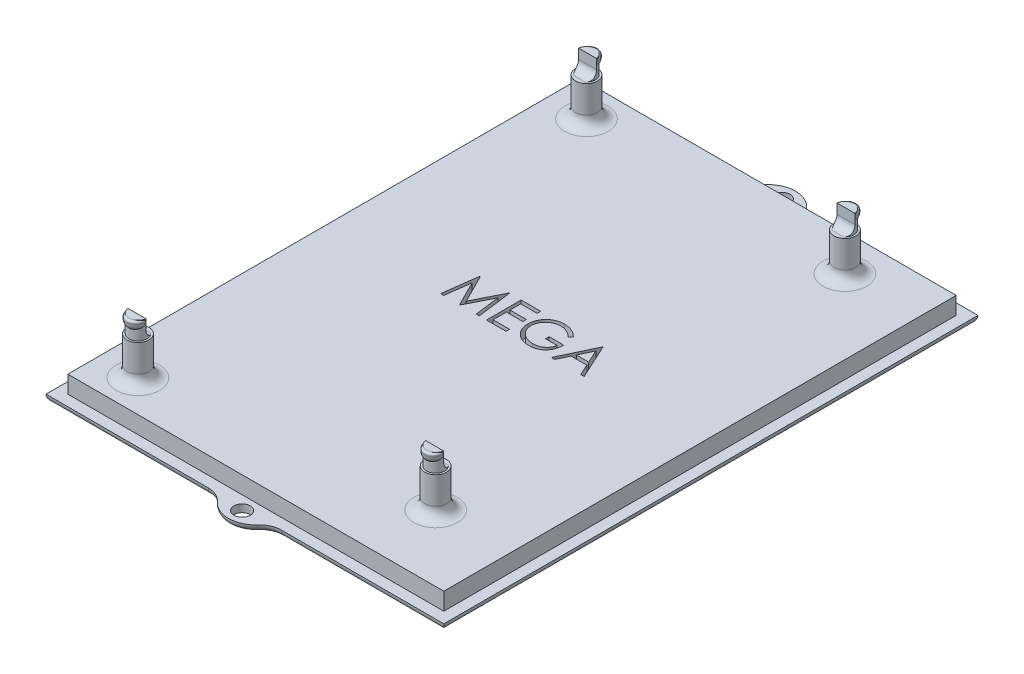
SolidWorks part; units mm, degrees
ref_plane "Front Plane" through (0, 0, 0) normal (0, 0, 1) x (1, 0, 0)
ref_plane "Top Plane" through (0, 0, 0) normal (0, 1, 0) x (1, 0, 0)
ref_plane "Right Plane" through (0, 0, 0) normal (1, 0, 0) x (0, 0, -1)
sketch "Sketch1" plane through (0, 0, 0) normal (0, 1, 0) x (1, 0, 0)
  line L0 (-34.45, 46.95) -> (34.45, 46.95)
  line L5 (-34.45, 46.95) -> (-34.45, -46.95)
  line L6 (-34.45, -46.95) -> (34.45, -46.95)
  line L7 (34.45, 46.95) -> (34.45, -46.95)
  point P11 (-34.45, 0)
  point P12 (0, -46.95)
  dimension "D3" = 93.9
  dimension "D4" = 68.9
extrude "Boss-Extrude1" add sketch "Sketch1" along normal blind 4.575
sketch "Sketch2" plane through (0, 4.575, 0) normal (0, 1, 0) x (1, 0, 0)
  line L0 (-27.45, 41.1) -> (20.81, 41.1) construction
  line L1 (-27.45, 41.1) -> (-27.45, -41.1) construction
  line L2 (20.81, 41.1) -> (20.81, 40.2) construction
  line L3 (20.81, -34.8) -> (-27.45, -34.8) construction
  line L4 (-34.45, 46.95) -> (-34.45, -46.95) construction
  line L6 (20.81, 40.2) -> (20.81, -34.8) construction
  circle A12 centre (-27.45, -41.1) radius 2
  circle A13 centre (-27.45, 41.1) radius 2
  circle A14 centre (20.81, 40.2) radius 2
  circle A15 centre (20.81, -34.8) radius 2
  point P3 (-27.45, 0)
  dimension "D7" = 7
  dimension "D6" = 75
  dimension "D2" = 4
  dimension "D1" = 82.2
  dimension "D3" = 0.9
  dimension "D4" = 48.26
extrude "Boss-Extrude2" add sketch "Sketch2" along normal blind 7
sketch "Sketch6" plane through (0, 0, 0) normal (0, -1, 0) x (1, 0, 0)
  line L8 (-36.45, 48.95) -> (-36.45, -48.95)
  line L9 (-36.45, -48.95) -> (36.45, -48.95)
  line L10 (36.45, -48.95) -> (36.45, 48.95)
  line L11 (36.45, 48.95) -> (-36.45, 48.95)
  line L12 (-36.45, 48.95) -> (-36.45, -48.95)
  line L13 (-36.45, -48.95) -> (36.45, -48.95)
  line L14 (36.45, -48.95) -> (36.45, 48.95)
  line L15 (36.45, 48.95) -> (-36.45, 48.95)
  dimension "D1" = 2
extrude "Boss-Extrude4" add sketch "Sketch6" against normal blind 1.4
sketch "Sketch4" plane through (0, 0, 0) normal (0, 1, 0) x (1, 0, 0)
  line L2 (36.45, -48.95) -> (-36.45, -48.95) construction
  line L4 (-34.45, -46.95) -> (34.45, -46.95) construction
  line L5 (-6.7082, -48.95) -> (6.7082, -48.95)
  arc A3 (-6.7082, -48.95) -> (-3.7268, -50.2833) centre (-6.7082, -52.95) cw
  arc A4 (-3.7268, -50.2833) -> (3.7268, -50.2833) centre (0, -46.95) ccw
  arc A5 (3.7268, -50.2833) -> (6.7082, -48.95) centre (6.7082, -52.95) cw
  dimension "D1" = 5
  dimension "D2" = 4
extrude "Boss-Extrude3" add sketch "Sketch4" along normal blind 1.4
sketch "Sketch7" plane through (0, 1.4, 0) normal (0, 1, 0) x (1, 0, 0)
  line L0 (0, -46.95) -> (0, -51.95) construction
  line L1 (34.45, -46.95) -> (-34.45, -46.95) construction
  arc A0 (-3.7268, -50.2833) -> (3.7268, -50.2833) centre (0, -46.95) ccw construction
  circle A1 centre (0, -49.45) radius 1.5
  dimension "D1" = 3
extrude "Cut-Extrude3" cut sketch "Sketch7" against normal up to next
mirror "Mirror1" about plane through (0, 0, 0) normal (0, 0, 1) of "Cut-Extrude3", "Boss-Extrude3"
sketch "Sketch5" plane through (0, 4.575, 0) normal (0, 1, 0) x (1, 0, 0)
  line L0 (-15, 0) -> (15, 0) construction
  text T0 "MEGA\r\n" font "Century Gothic" height in points 24
  point P6 (0, 0)
  dimension "D1" = 30
extrude "Cut-Extrude2" cut sketch "Sketch5" against normal blind 2
fillet "Fillet1" radius 1.4 12 edges at (-21.5791, 0, 48.95) (-5.0752, 0, 49.2985) (21.5791, 0, 48.95) (5.0752, 0, 49.2985) (0, 0, 51.95) (36.45, 0, 0) (21.5791, 0, -48.95) (5.0752, 0, -49.2985) (0, 0, -51.95) (-5.0752, 0, -49.2985) (-21.5791, 0, -48.95) (-36.45, 0, 0)
sketch "Sketch8" plane through (0, 11.575, 0) normal (0, 1, 0) x (1, 0, 0)
  circle A4 centre (-27.45, 41.1) radius 1.65
  circle A5 centre (20.81, 40.2) radius 1.65
  circle A6 centre (20.81, -34.8) radius 1.65
  circle A7 centre (-27.45, -41.1) radius 1.65
  dimension "D1" = 3.3
extrude "Boss-Extrude5" add sketch "Sketch8" along normal blind 1.3
sketch "Sketch9" plane through (0, 12.875, 0) normal (0, 1, 0) x (1, 0, 0)
  line L0 (-27.45, 42.75) -> (-27.45, 39.45) construction
  line L1 (20.81, 38.55) -> (20.81, 41.85) construction
  line L2 (-27.45, -39.45) -> (-27.45, -42.75) construction
  line L3 (20.81, -33.15) -> (20.81, -36.45) construction
  arc A0 (-25.8122, 41.3) -> (-29.0878, 41.3) centre (-27.45, 41.5) ccw
  circle A1 centre (-27.45, 41.1) radius 1.65 construction
  arc A2 (-29.0878, 41.3) -> (-25.8122, 41.3) centre (-27.45, 41.1) ccw
  arc A3 (22.4478, 40.4) -> (19.1722, 40.4) centre (20.81, 40.6) ccw
  arc A4 (19.1722, 40.4) -> (22.4478, 40.4) centre (20.81, 40.2) ccw
  circle A5 centre (20.81, 40.2) radius 1.65 construction
  arc A6 (-25.8122, -41.3) -> (-29.0878, -41.3) centre (-27.45, -41.1) ccw
  arc A7 (-29.0878, -41.3) -> (-25.8122, -41.3) centre (-27.45, -41.5) ccw
  circle A8 centre (20.81, 40.2) radius 1.65 construction
  circle A11 centre (-27.45, -41.1) radius 1.65 construction
  arc A12 (22.4478, -35) -> (19.1722, -35) centre (20.81, -34.8) ccw
  circle A14 centre (-27.45, -41.1) radius 1.65 construction
  arc A15 (19.1722, -35) -> (22.4478, -35) centre (20.81, -35.2) ccw
  circle A16 centre (20.81, -34.8) radius 1.65 construction
  point P8 (-27.45, 41.1)
  point P15 (20.81, 40.2)
  point P17 (0, 0)
  point P18 (0, 0)
  point P21 (20.81, 38.7)
  point P27 (-27.45, -41.1)
  point P31 (-27.45, -42.6)
  point P37 (20.81, -34.8)
  point P39 (16.0642, -35.9935)
  point P42 (-23.793, 44.9389)
  point P45 (0, 0)
  point P46 (-27.45, -43.0003)
  point P47 (0, 0)
  point P48 (0, 0)
  point P49 (0, 0)
  point P50 (0, 0)
  point P51 (0, 0)
  point P52 (0, 0)
  point P53 (0, 0)
  point P54 (0, 0)
  point P55 (0, 0)
  point P56 (0, 0)
  point P57 (0, 0)
  point P60 (-27.45, -39.45)
  point P61 (-28.7241, -42.1484)
  point P62 (-29.0138, -40.5737)
  point P63 (-29.0508, -41.5)
  point P64 (20.81, -33.15)
  dimension "D1" = 0.4
  dimension "D3" = 0.4
  dimension "D2" = 0.4
  dimension "D5" = 0.4
extrude "Boss-Extrude6" add sketch "Sketch9" along normal blind 2
fillet "Fillet2" radius 1.4 4 edges at (-27.45, 12.875, -43.15) (20.81, 12.875, -42.25) (-27.45, 12.875, 43.15) (20.81, 12.875, 36.85)
fillet "Fillet3" radius 0.4 4 edges at (-27.45, 14.875, -43.15) (-27.45, 14.875, 43.15) (20.81, 14.875, -42.25) (20.81, 14.875, 36.85)
fillet "Fillet4" radius 2 4 edges at (-27.45, 4.575, 43.1) (20.81, 4.575, 36.8) (20.81, 4.575, -38.2) (-27.45, 4.575, -39.1)
sketch "Sketch10" plane through (0, 14.875, 0) normal (0, 1, 0) x (1, 0, 0)
  line L1 (22.46, -35) -> (19.16, -35)
  line L2 (22.46, -35) -> (22.46, -33.15)
  line L3 (22.46, -33.15) -> (19.16, -33.15)
  line L4 (19.16, -35) -> (19.16, -33.15)
  line L5 (-29.1, -41.3) -> (-25.8, -41.3)
  line L6 (-29.1, -41.3) -> (-29.1, -39.45)
  line L7 (-29.1, -39.45) -> (-25.8, -39.45)
  line L8 (-25.8, -41.3) -> (-25.8, -39.45)
  line L9 (-29.1, 41.3) -> (-25.8, 41.3)
  line L10 (-29.1, 41.3) -> (-29.1, 39.45)
  line L11 (-29.1, 39.45) -> (-25.8, 39.45)
  line L12 (-25.8, 41.3) -> (-25.8, 39.45)
  line L13 (19.16, 40.4) -> (22.46, 40.4)
  line L14 (19.16, 40.4) -> (19.16, 38.55)
  line L15 (19.16, 38.55) -> (22.46, 38.55)
  line L16 (22.46, 40.4) -> (22.46, 38.55)
  circle A2 centre (20.81, -34.8) radius 1.65 construction
  circle A3 centre (20.81, -34.8) radius 1.65 construction
  circle A4 centre (-27.45, -41.1) radius 1.65 construction
  circle A6 centre (-27.45, 41.1) radius 1.65 construction
  circle A7 centre (-27.45, 41.1) radius 1.65 construction
  circle A8 centre (20.81, 40.2) radius 1.65 construction
  point P15 (0, 0)
  point P16 (0, 0)
  point P30 (0, 0)
  point P31 (0, 0)
  point P32 (0, 0)
  point P34 (0, 0)
  point P35 (0, 0)
  point P37 (0, 0)
  point P38 (0, 0)
  point P39 (0, 0)
  point P41 (0, 0)
extrude "Cut-Extrude4" cut sketch "Sketch10" against normal up to surface (3.3 mm away) up to face at (20.81, 11.575, -38.55)
fillet "Fillet5" radius 1.5 4 edges at (-27.45, 11.575, 41.3) (20.81, 11.575, -40.4) (-27.45, 11.575, -41.3) (20.81, 11.575, 35)
